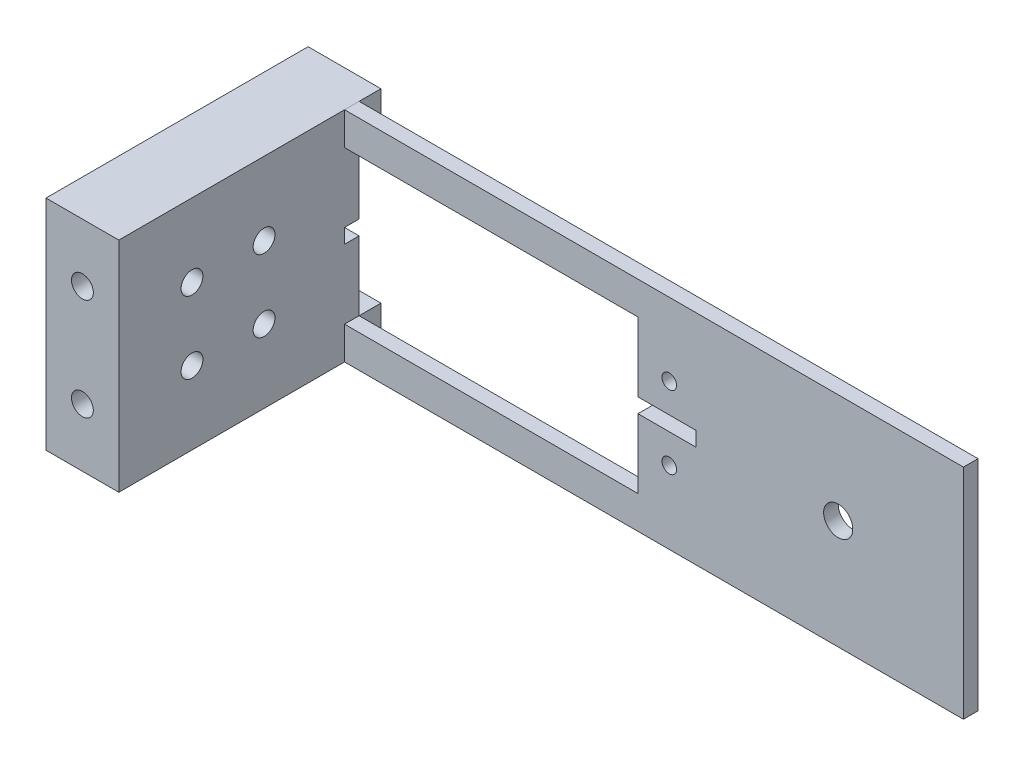
SolidWorks part; units mm, degrees
ref_plane "Спереди" through (0, 0, 0) normal (0, 0, 1) x (1, 0, 0)
ref_plane "Сверху" through (0, 0, 0) normal (0, 1, 0) x (1, 0, 0)
ref_plane "Справа" through (0, 0, 0) normal (1, 0, 0) x (0, 0, -1)
sketch "Эскиз1" plane through (0, 0, 0) normal (0, 1, 0) x (1, 0, 0)
  line L0 (10, 0) -> (10, 31)
  line L1 (0, 0) -> (10, 0)
  line L2 (0, 0) -> (0, 36)
  line L3 (0, 36) -> (10, 36)
  line L4 (10, 0) -> (9.7456, 0.0582)
  line L5 (10, 31) -> (95, 31)
  line L6 (95, 31) -> (95, 33)
  line L7 (95, 33) -> (10, 33)
  line L8 (10, 33) -> (10, 36)
  dimension "D1" = 36
  dimension "D2" = 3
  dimension "D3" = 10
  dimension "D4" = 31
extrude "Бобышка-Вытянуть1" add sketch "Эскиз1" along normal blind 30 contours L5 L6 L3 L2 L1 L0 region at (5, 0, -1.0159)
sketch "Эскиз2" plane through (0, 0, 0) normal (-1, 0, 0) x (0, 0, 1)
  line L0 (-15, 22) -> (-22, 15) construction
  line L1 (-18.5, 18.5) -> (-19.9497, 19.9497) construction
  line L2 (-18.5, 18.5) -> (-10.0503, 10.0503) construction
  line L3 (0, 30) -> (0, 0) construction
  line L4 (0, 0) -> (-36, 0) construction
  line L5 (-15, 15) -> (-10.0503, 19.9497) construction
  line L6 (-15, 15) -> (-19.9497, 10.0503) construction
  circle A0 centre (-15, 15) radius 7 construction
  circle A1 centre (-19.9497, 19.9497) radius 1.5
  circle A2 centre (-10.0503, 19.9497) radius 1.5
  circle A3 centre (-19.9497, 10.0503) radius 1.5
  circle A4 centre (-10.0503, 10.0503) radius 1.5
  circle A5 centre (-15, 15) radius 8.5 construction
  dimension "D1" = 14
  dimension "D4" = 17
  dimension "D2" = 15
  dimension "D3" = 15
extrude "Вырез-Вытянуть1" cut sketch "Эскиз2" against normal through all
sketch "Эскиз3" plane through (0, 0, -36) normal (0, 0, -1) x (-1, 0, 0)
  line L1 (-10, 25.5) -> (-50.3, 25.5)
  line L2 (-10, 25.5) -> (-10, 4.5)
  line L3 (-10, 4.5) -> (-50.3, 4.5)
  line L4 (-50.3, 25.5) -> (-50.3, 4.5)
  line L5 (0, 30) -> (0, 0) construction
  point P4 (-10, 15)
  point P5 (0, 15)
  dimension "D1" = 21
  dimension "D3" = 10
  dimension "D4" = 40.3
extrude "Вырез-Вытянуть2" cut sketch "Эскиз3" against normal through all
sketch "Эскиз4" plane through (0, 0, -36) normal (0, 0, -1) x (-1, 0, 0)
  line L5 (-10, 4.5) -> (-2, 4.5)
  line L6 (-10, 4.5) -> (-10, 25.5)
  line L7 (-10, 25.5) -> (-2, 25.5)
  line L8 (-2, 4.5) -> (-2, 25.5)
  line L9 (-10, 25.5) -> (-50.3, 25.5) construction
  dimension "D2" = 8
extrude "Вырез-Вытянуть3" cut sketch "Эскиз4" against normal blind 3
sketch "Эскиз5" plane through (0, 0, -36) normal (0, 0, -1) x (-1, 0, 0)
  line L0 (-2, 4.5) -> (-2, 25.5) construction
  line L1 (-58.3, 16) -> (-2, 16)
  line L2 (-58.3, 14) -> (-2, 14)
  line L4 (-2, 16) -> (-2, 14)
  line L8 (-2, 16) -> (-58.3, 16) construction
  line L9 (-58.3, 14) -> (-58.3, 16)
  line L15 (-2, 14) -> (-58.3, 14) construction
  point P8 (-2, 15)
  point P12 (-2, 15)
  dimension "D1" = 56.3
  dimension "D2" = 2
extrude "Вырез-Вытянуть4" cut sketch "Эскиз5" against normal blind 5
sketch "Эскиз6" plane through (0, 0, -33) normal (0, 0, -1) x (-1, 0, 0)
  line L1 (-10, 16) -> (-10, 14) construction
  line L2 (-5.4, 10) -> (-5.4, 20) construction
  line L3 (-5.4, 10) -> (-54.6, 10) construction
  line L4 (-10, 30) -> (-10, 25.5) construction
  line L5 (-5.4, 11) -> (-54.6, 11) construction
  line L6 (-4.4, 10) -> (-4.4, 22.6602) construction
  line L7 (-5.4, 20) -> (-54.6, 20) construction
  line L8 (-5.4, 21) -> (-54.6, 21) construction
  line L9 (-54.6, 10) -> (-54.6, 21) construction
  circle A0 centre (-5.4, 10) radius 1
  circle A1 centre (-54.6, 10) radius 1
  circle A2 centre (-5.4, 20) radius 1
  circle A3 centre (-54.6, 20) radius 1
  point P6 (-10, 15)
  dimension "D1" = 4.6
  dimension "D3" = 2
  dimension "D4" = 49.2
  dimension "D5" = 10
  dimension "D2" = 5
extrude "Вырез-Вытянуть5" cut sketch "Эскиз6" against normal blind 4
sketch "Эскиз7" plane through (0, 0, -36) normal (0, 0, -1) x (-1, 0, 0)
  line L0 (-95, 30) -> (-95, 0) construction
  line L1 (-77.8, 15) -> (-95, 15) construction
  line L4 (-50.3, 4.5) -> (-50.3, 14) construction
  circle A0 centre (-77.8, 15) radius 2
  dimension "D1" = 27.5
  dimension "D2" = 4
extrude "Вырез-Вытянуть6" cut sketch "Эскиз7" against normal through all
sketch "Эскиз8" plane through (0, 0, 0) normal (0, 0, 1) x (1, 0, 0)
  line L0 (5, 30) -> (5, 0) construction
  line L1 (0, 30) -> (10, 30) construction
  line L2 (0, 0) -> (10, 0) construction
  line L3 (3.5, 22) -> (3.5, 8) construction
  circle A0 centre (5, 22) radius 1.5
  circle A1 centre (5, 8) radius 1.5
  dimension "D1" = 3
  dimension "D2" = 8
  dimension "D3" = 14
extrude "Вырез-Вытянуть7" cut sketch "Эскиз8" against normal blind 4
split "Разделить1" bodies to split 113 resulting bodies 111 112 split by face at (10, 15, -26.5)
